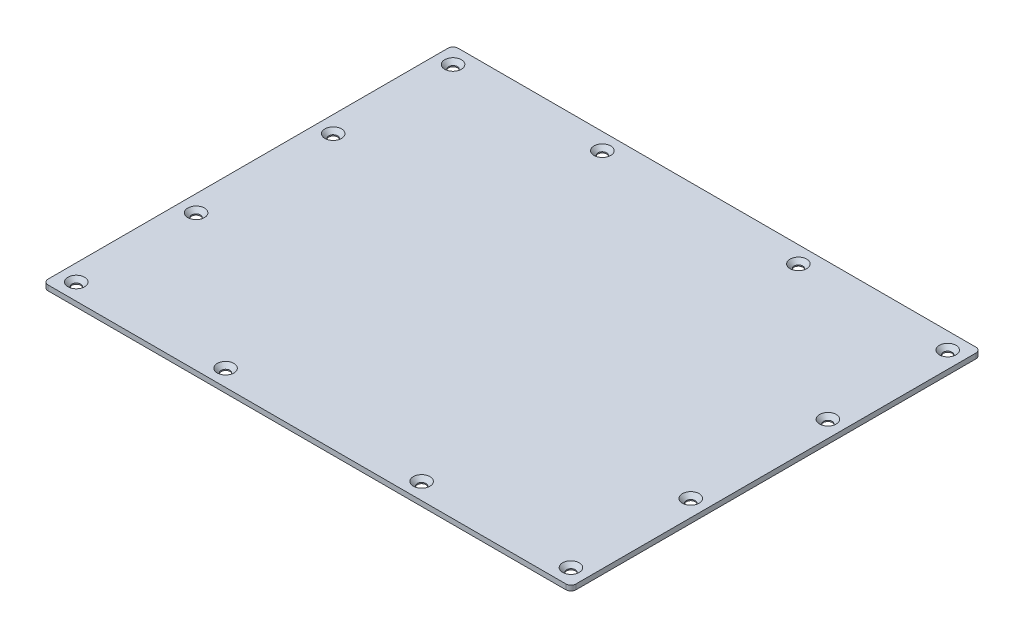
SolidWorks part; units mm, degrees
ref_plane "Front Plane" through (0, 0, 0) normal (0, 0, 1) x (1, 0, 0)
ref_plane "Top Plane" through (0, 0, 0) normal (0, 1, 0) x (1, 0, 0)
ref_plane "Right Plane" through (0, 0, 0) normal (1, 0, 0) x (0, 0, -1)
sketch "Sketch1" plane through (0, 0, 0) normal (0, 1, 0) x (1, 0, 0)
  line L0 (-103, 78) -> (-103, -78) construction
  line L1 (-101, -80) -> (101, -80) construction
  line L2 (103, -78) -> (103, 78) construction
  line L4 (101, 80) -> (-101, 80) construction
  line L31 (103, -78) -> (103, 78)
  line L32 (-101, -80) -> (101, -80)
  line L33 (101, 80) -> (-101, 80)
  line L34 (-103, 78) -> (-103, -78)
  arc A0 (-101, 80) -> (-103, 78) centre (-101, 78) ccw construction
  arc A1 (103, 78) -> (101, 80) centre (101, 78) ccw construction
  arc A2 (101, -80) -> (103, -78) centre (101, -78) ccw construction
  arc A3 (-103, -78) -> (-101, -80) centre (-101, -78) ccw construction
  arc A29 (103, 78) -> (101, 80) centre (101, 78) ccw
  arc A30 (101, -80) -> (103, -78) centre (101, -78) ccw
  arc A31 (-103, -78) -> (-101, -80) centre (-101, -78) ccw
  arc A32 (-101, 80) -> (-103, 78) centre (-101, 78) ccw
extrude "Boss-Extrude1" add sketch "Sketch1" along normal blind 2
ref_axis "Axis1" through (0, 2.1, 0) along (0, -1, 0)
sketch "Sketch2" plane through (0, 2, 0) normal (0, 1, 0) x (1, 0, 0)
  circle A0 centre (-38.25, 73.5) radius 1.4 construction
  circle A1 centre (38.25, 73.5) radius 1.4 construction
  circle A2 centre (96.5, 26.75) radius 1.4 construction
  circle A3 centre (38.25, -73.5) radius 1.4 construction
  circle A12 centre (-38.25, -73.5) radius 1.4 construction
  circle A13 centre (-96.5, -26.75) radius 1.4 construction
  circle A14 centre (-96.5, 26.75) radius 1.4 construction
  circle A15 centre (-38.25, 73.5) radius 1.4
  circle A16 centre (38.25, 73.5) radius 1.4
  circle A17 centre (96.5, 26.75) radius 1.4
  circle A18 centre (38.25, -73.5) radius 1.4
  circle A19 centre (-38.25, -73.5) radius 1.4
  circle A20 centre (-96.5, -26.75) radius 1.4
  circle A21 centre (-96.5, 26.75) radius 1.4
  circle A22 centre (-96.5, -73.5) radius 1.4 construction
  circle A23 centre (96.5, -73.5) radius 1.4 construction
  circle A24 centre (96.5, 73.5) radius 1.4 construction
  circle A25 centre (-96.5, 73.5) radius 1.4 construction
  circle A26 centre (-96.5, -73.5) radius 1.4
  circle A27 centre (96.5, -73.5) radius 1.4
  circle A28 centre (96.5, 73.5) radius 1.4
  circle A29 centre (-96.5, 73.5) radius 1.4
  circle A30 centre (96.5, -26.75) radius 1.4 construction
  circle A31 centre (96.5, -26.75) radius 1.4
hole_wizard "CSK for M3 Flat Head Machine Screw1" positions "3DSketch1" profile "Sketch3" countersink size "M3" standard "ANSI Metric" end condition through all
sketch3d "3DSketch1"
  point P0 (-96.5, 2, -73.5)
  point P3 (-96.5, 2, -26.75)
  point P6 (-38.25, 2, -73.5)
  point P9 (38.25, 2, -73.5)
  point P12 (96.5, 2, -73.5)
  point P15 (96.5, 2, -26.75)
  point P18 (96.5, 2, 26.75)
  point P21 (96.5, 2, 73.5)
  point P24 (38.25, 2, 73.5)
  point P27 (-38.25, 2, 73.5)
  point P30 (-96.5, 2, 73.5)
  point P33 (-96.5, 2, 26.75)
sketch "Sketch3" plane through (-96.5, 2, -73.5) normal (1, 0, 0) x (0, 0, 1)
  line L0 (0, 0) -> (0, 2)
  line L1 (0, 2) -> (1.725, 2)
  line L2 (1.7, 1.975) -> (1.7, 1.55)
  line L3 (1.7, 1.55) -> (3.25, 0)
  line L5 (3.25, 0) -> (0, 0)
  line L6 (-1.7, 1.55) -> (-3.25, 0) construction
  line L7 (1.725, 2) -> (1.7, 1.975)
  line L8 (-1.725, 2) -> (-1.7, 1.975) construction
  line L11 (0, -6.35) -> (0, 107.95) construction
  dimension "Thru Hole Dia." = 3.4
  dimension "Thru Hole Depth" = 2
  dimension "Near C'Sink Dia." = 6.5
  dimension "Near C'Sink Angle" = 90
  dimension "Far C'Sink Dia." = 3.45
  dimension "Far C'Sink Angle" = 90
sketch "Sketch4" plane through (0, 0, 0) normal (0, -1, 0) x (1, 0, 0)
  line L4 (103, -78) -> (103, 78)
  line L5 (101, 80) -> (-101, 80)
  line L6 (-103, 78) -> (-103, -78)
  line L7 (-101, -80) -> (101, -80)
  line L8 (103, -78) -> (103, 78)
  line L9 (101, 80) -> (-101, 80)
  line L10 (-103, 78) -> (-103, -78)
  line L11 (-101, -80) -> (101, -80)
  line L16 (102.2, -78) -> (102.2, 78)
  line L17 (101, 79.2) -> (-101, 79.2)
  line L18 (-102.2, 78) -> (-102.2, -78)
  line L19 (-101, -79.2) -> (101, -79.2)
  line L20 (102.2, -78) -> (102.2, 78)
  line L21 (101, 79.2) -> (-101, 79.2)
  line L22 (-102.2, 78) -> (-102.2, -78)
  line L23 (-101, -79.2) -> (101, -79.2)
  arc A4 (101, -80) -> (103, -78) centre (101, -78) ccw
  arc A5 (103, 78) -> (101, 80) centre (101, 78) ccw
  arc A6 (-101, 80) -> (-103, 78) centre (-101, 78) ccw
  arc A7 (-103, -78) -> (-101, -80) centre (-101, -78) ccw
  arc A8 (101, -80) -> (103, -78) centre (101, -78) ccw
  arc A9 (103, 78) -> (101, 80) centre (101, 78) ccw
  arc A10 (-101, 80) -> (-103, 78) centre (-101, 78) ccw
  arc A11 (-103, -78) -> (-101, -80) centre (-101, -78) ccw
  arc A16 (101, -79.2) -> (102.2, -78) centre (101, -78) ccw
  arc A17 (102.2, 78) -> (101, 79.2) centre (101, 78) ccw
  arc A18 (-101, 79.2) -> (-102.2, 78) centre (-101, 78) ccw
  arc A19 (-102.2, -78) -> (-101, -79.2) centre (-101, -78) ccw
  arc A20 (101, -79.2) -> (102.2, -78) centre (101, -78) ccw
  arc A21 (102.2, 78) -> (101, 79.2) centre (101, 78) ccw
  arc A22 (-101, 79.2) -> (-102.2, 78) centre (-101, 78) ccw
  arc A23 (-102.2, -78) -> (-101, -79.2) centre (-101, -78) ccw
  dimension "D1" = 0
  dimension "D2" = 0.8
